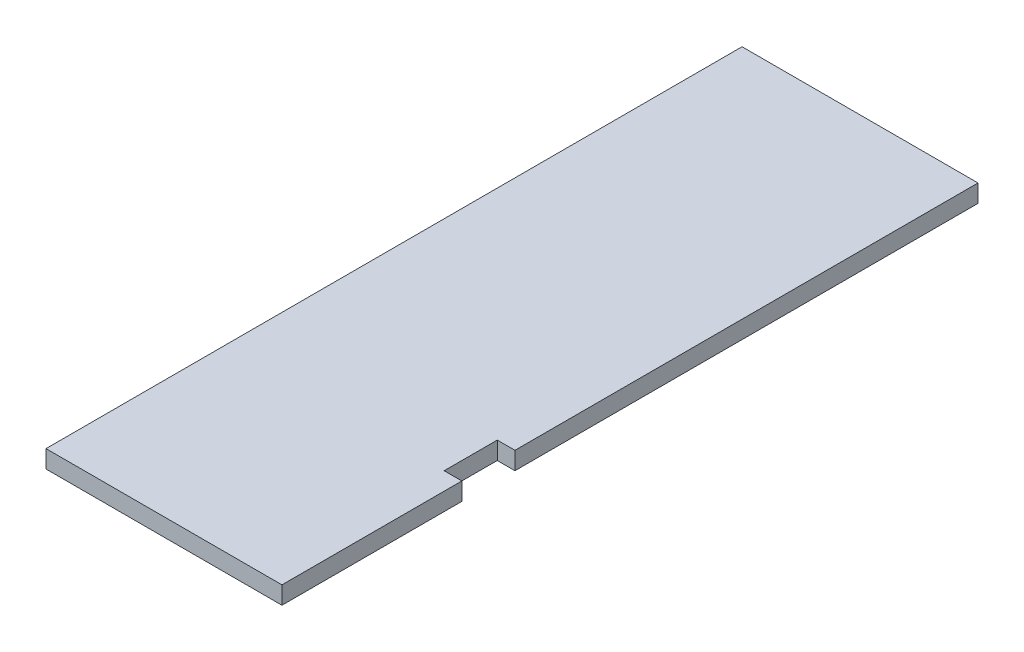
SolidWorks part; units mm, degrees
material "Acrilico TEC"
ref_plane "Front Plane" through (0, 0, 0) normal (0, 0, 1) x (1, 0, 0)
ref_plane "Top Plane" through (0, 0, 0) normal (0, 1, 0) x (1, 0, 0)
ref_plane "Right Plane" through (0, 0, 0) normal (1, 0, 0) x (0, 0, -1)
sketch "Sketch1" plane through (0, 0, 0) normal (0, 1, 0) x (1, 0, 0)
  line L1 (0, 0) -> (40, 0)
  line L2 (0, 0) -> (0, 98)
  line L3 (0, 98) -> (40, 98)
  line L4 (40, 0) -> (40, 98)
  dimension "D1" = 40
  dimension "D2" = 98
extrude "Boss-Extrude1" add sketch "Sketch1" along normal blind 3
sketch "Sketch4" plane through (0, 0, 0) normal (0, 0, 1) x (1, 0, 0)
  line L1 (0, 0) -> (40, 0)
  line L2 (0, 0) -> (0, 3)
  line L3 (0, 3) -> (40, 3)
  line L4 (40, 0) -> (40, 3)
extrude "Boss-Extrude3" add sketch "Sketch4" along normal blind 20
sketch "Sketch9" plane through (0, 3, 0) normal (0, 1, 0) x (1, 0, 0)
  line L1 (37, 10.5) -> (40, 10.5)
  line L2 (37, 10.5) -> (37, 19.5)
  line L3 (37, 19.5) -> (40, 19.5)
  line L4 (40, 10.5) -> (40, 19.5)
  dimension "D1" = 9
  dimension "D2" = 3
extrude "Cut-Extrude1" cut sketch "Sketch9" against normal blind 10
